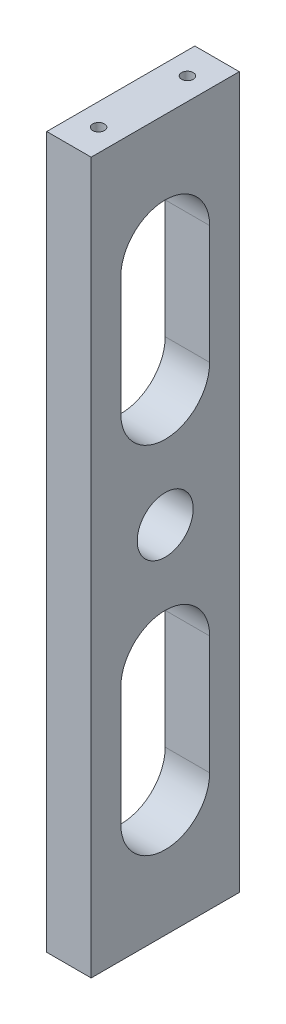
SolidWorks part; units mm, degrees
material "6061 Alloy"
ref_plane "Front Plane" through (0, 0, 0) normal (0, 0, 1) x (1, 0, 0)
ref_plane "Top Plane" through (0, 0, 0) normal (0, 1, 0) x (1, 0, 0)
ref_plane "Right Plane" through (0, 0, 0) normal (1, 0, 0) x (0, 0, -1)
sketch "Sketch1" plane through (0, 0, 0) normal (1, 0, 0) x (0, 0, -1)
  line L1 (-15.875, -76.2) -> (15.875, -76.2)
  line L2 (-15.875, -76.2) -> (-15.875, 76.2)
  line L3 (-15.875, 76.2) -> (15.875, 76.2)
  line L4 (15.875, -76.2) -> (15.875, 76.2)
  line L5 (-15.875, -76.2) -> (15.875, 76.2) construction
  line L6 (-15.875, 76.2) -> (15.875, -76.2) construction
  point P0 (0, 0)
  dimension "D1" = 31.75
  dimension "D2" = 152.4
extrude "Boss-Extrude1" add sketch "Sketch1" along normal mid plane 9.525
sketch "Sketch2" plane through (0, 76.2, 0) normal (0, 1, 0) x (1, 0, 0)
  line L0 (0, 9.525) -> (0, -9.525) construction
  line L1 (-4.7625, 15.875) -> (-4.7625, -15.875) construction
  line L2 (4.7625, 15.875) -> (-4.7625, 15.875) construction
  point P2 (0, 0)
  point P5 (-4.7625, 0)
  point P8 (0, 15.875)
  point P10 (0, 9.525)
  point P11 (0, -9.525)
  dimension "D1" = 19.05
hole_wizard "M3x0.5 Tapped Hole1" positions "Sketch3" profile "Sketch4" tap size "M3x0.5" standard "ANSI Metric"
sketch "Sketch3" plane through (0, 76.2, 0) normal (0, 1, 0) x (1, 0, 0)
  point P0 (0, 9.525)
  point P3 (0, -9.525)
sketch "Sketch4" plane through (0, 76.2, -9.525) normal (1, 0, 0) x (0, 0, 1)
  line L0 (0, 0) -> (0, 13.4511)
  line L1 (0, 13.4511) -> (1.25, 12.7)
  line L2 (1.25, 12.7) -> (1.25, 0)
  line L5 (1.25, 0) -> (0, 0)
  line L10 (0, 13.4511) -> (-1.25, 12.7) construction
  line L11 (0, -6.35) -> (0, 107.95) construction
  dimension "Tap Drill Dia." = 2.5
  dimension "Tap Drill Depth" = 12.7
  dimension "Drill Angle" = 118
cosmetic thread "Hole Thread1" parameters "D1"=6.096, "D2"=3
cosmetic thread "Hole Thread2" parameters "D1"=6.096, "D2"=3
mirror "Mirror1" about plane through (0, 0, 0) normal (0, 1, 0) of "M3x0.5 Tapped Hole1"
cosmetic thread "Hole Thread3" parameters "D1"=6.096, "D2"=3
cosmetic thread "Hole Thread4" parameters "D1"=6.096, "D2"=3
sketch "Sketch5" plane through (4.7625, 0, 0) normal (1, 0, 0) x (0, 0, -1)
  point P0 (0, 0)
hole_wizard "Ø12.0mm Dowel Hole1" positions "Sketch6" profile "Sketch8" hole size "Ø12.0" standard "ANSI Metric" end condition through all
sketch "Sketch6" plane through (4.7625, 0, 0) normal (1, 0, 0) x (0, 0, -1)
  point P0 (0, 0)
sketch "Sketch8" plane through (4.7625, 0, 0) normal (0, 1, 0) x (0, 0, -1)
  line L0 (0, 0) -> (0, 9.525)
  line L1 (0, 9.525) -> (6, 9.525)
  line L2 (6, 9.525) -> (6, 0)
  line L5 (6, 0) -> (0, 0)
  line L11 (0, -6.35) -> (0, 107.95) construction
  dimension "Thru Hole Dia." = 12
  dimension "Thru Hole Depth" = 9.525
sketch "Sketch9" plane through (4.7625, 0, 0) normal (1, 0, 0) x (0, 0, -1)
  line L0 (0, 50.8) -> (0, 25.4) construction
  line L1 (0, 55) -> (0, -55) construction
  line L2 (9.525, 50.8) -> (9.525, 25.4)
  line L3 (-9.525, 50.8) -> (-9.525, 25.4)
  line L4 (0, -25.4) -> (0, -50.8) construction
  line L5 (9.525, -25.4) -> (9.525, -50.8)
  line L6 (-9.525, -25.4) -> (-9.525, -50.8)
  line L7 (0, 25.4) -> (0, -25.4)
  line L8 (55, 0) -> (-55, 0) construction
  arc A0 (9.525, 50.8) -> (-9.525, 50.8) centre (0, 50.8) ccw
  arc A1 (-9.525, 25.4) -> (9.525, 25.4) centre (0, 25.4) ccw
  arc A2 (9.525, -25.4) -> (-9.525, -25.4) centre (0, -25.4) ccw
  arc A3 (-9.525, -50.8) -> (9.525, -50.8) centre (0, -50.8) ccw
  point P5 (0, 38.1)
  point P10 (0, -38.1)
  point P19 (0, 0)
  point P22 (0, -39.1179)
  dimension "D1" = 25.4
  dimension "D2" = 19.05
  dimension "D3" = 25.4
extrude "Cut-Extrude1" cut sketch "Sketch9" against normal through all contours L6 A3 L5 A2 | L3 A1 L2 A0 region at (4.7625, -38.1, 0) region at (4.7625, 38.1, 0)
